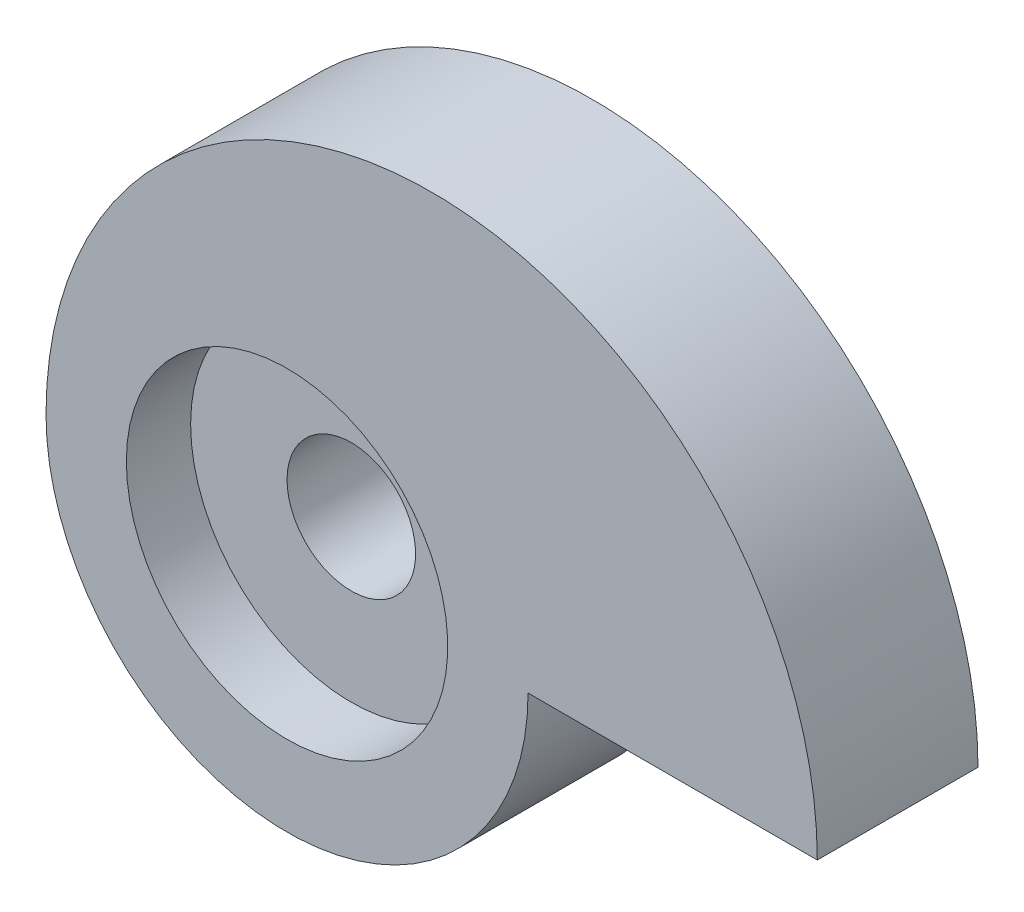
SolidWorks part; units mm, degrees
ref_plane "Front Plane" through (0, 0, 0) normal (0, 0, 1) x (1, 0, 0)
ref_plane "Top Plane" through (0, 0, 0) normal (0, 1, 0) x (1, 0, 0)
ref_plane "Right Plane" through (0, 0, 0) normal (1, 0, 0) x (0, 0, -1)
sketch "Sketch1" plane through (0, 0, 0) normal (0, 0, 1) x (1, 0, 0)
  line L0 (-12, 0) -> (12, 0) construction
  line L2 (3, 0) -> (12, 0)
  arc A0 (12, 0) -> (-12, 0) centre (0, 0) ccw
  circle A3 centre (-4.5, 0) radius 2
  arc A4 (-12, 0) -> (3, 0) centre (-4.5, 0) ccw
  dimension "D1" = 24
  dimension "D2" = 4
  dimension "D3" = 7.5
extrude "Boss-Extrude1" add sketch "Sketch1" along normal blind 5
sketch "Sketch3" plane through (0, 0, 0) normal (0, 0, 1) x (1, 0, 0)
  circle A0 centre (-4.5, 0) radius 5
  circle A1 centre (-4.5, 0) radius 2 construction
  circle A2 centre (-4.5, 0) radius 2
  dimension "D1" = 10
extrude "Boss-Extrude2" add sketch "Sketch3" against normal blind 5
sketch "Sketch4" plane through (0, 0, -5) normal (0, 0, -1) x (-1, 0, 0)
  line L1 (-2.0014, -1) -> (11.0014, -1)
  line L2 (-2.0014, -1) -> (-2.0014, 1)
  line L3 (-2.0014, 1) -> (11.0014, 1)
  line L4 (11.0014, -1) -> (11.0014, 1)
  line L5 (-2.0014, -1) -> (11.0014, 1) construction
  line L6 (-2.0014, 1) -> (11.0014, -1) construction
  point P0 (4.5, 0)
  dimension "D1" = 2
extrude "Cut-Extrude1" cut sketch "Sketch4" against normal blind 3
fillet "Fillet1" radius 1 4 edges at (-7.8155, 1, -2) (-7.8155, -1, -2) (-1.1845, -1, -2) (-1.1845, 1, -2)
sketch "Sketch5" plane through (0, 0, 5) normal (0, 0, -1) x (-1, 0, 0)
  circle A1 centre (4.5, 0) radius 5
  circle A2 centre (4.5, 0) radius 2 construction
  dimension "D1" = 10
extrude "Cut-Extrude2" cut sketch "Sketch5" along normal blind 2
fillet "Fillet2" radius 1.5 1 edges at (0.5, 0, 0)
fillet "Fillet3" [suppressed] radius 1
